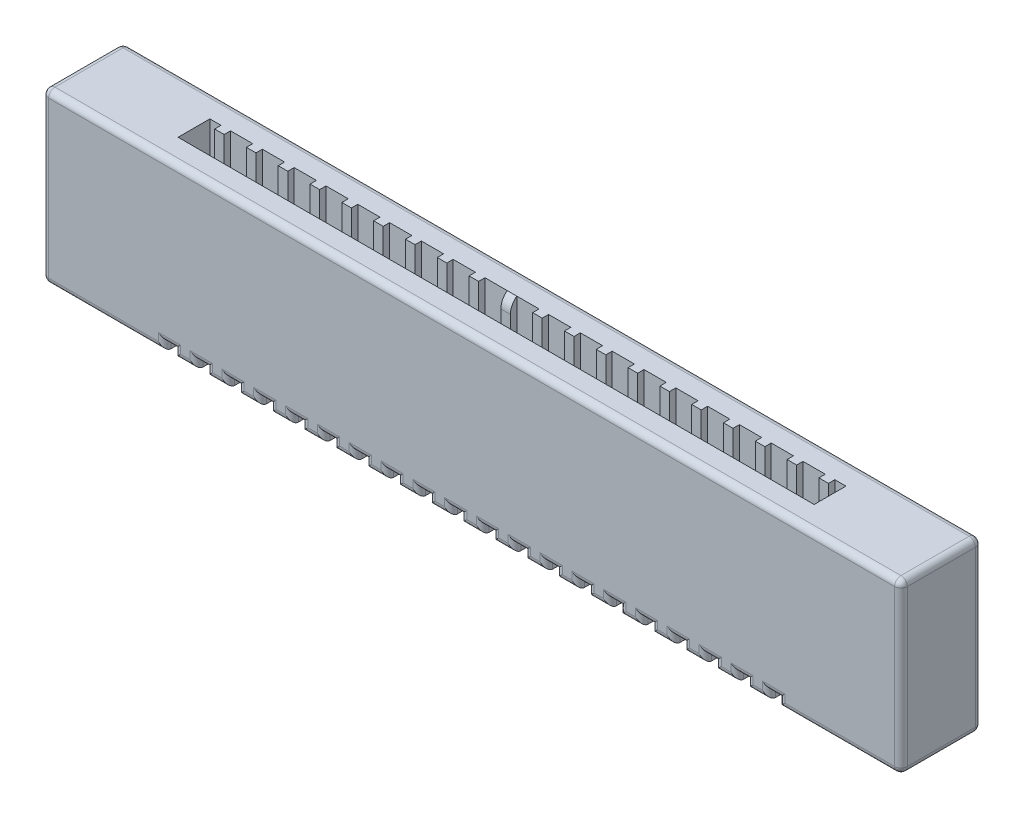
SolidWorks part; units mm, degrees
ref_plane "前视基准面" through (0, 0, 0) normal (0, 0, 1) x (1, 0, 0)
ref_plane "上视基准面" through (0, 0, 0) normal (0, 1, 0) x (1, 0, 0)
ref_plane "右视基准面" through (0, 0, 0) normal (1, 0, 0) x (0, 0, -1)
sketch "草图1" plane through (0, 0, 0) normal (0, 0, 1) x (1, 0, 0)
  line L0 (-1000, 0) -> (49000, 0) construction
  line L1 (0, -1000) -> (0, 49000) construction
  line L2 (-13.5, 2.65) -> (-13.5, -2.65)
  line L3 (-13.5, -2.65) -> (13.5, -2.65)
  line L4 (-13.5, 2.65) -> (13.5, 2.65)
  line L5 (13.5, 2.65) -> (13.5, -2.65)
  point P10 (-13.5, 0)
  point P11 (0, -2.65)
  point P12 (0, 2.65)
  dimension "D1" = 5.3
  dimension "D2" = 27
extrude "凸台-拉伸1" add sketch "草图1" along normal blind 2.54
sketch "草图2" plane through (0, -2.65, 0) normal (0, -1, 0) x (1, 0, 0)
  line L0 (0, 2.54) -> (0, 0) construction
  line L1 (-13.5, 2.54) -> (13.5, 2.54) construction
  line L2 (0.5, 2.54) -> (0.5, 0) construction
  line L3 (-13.5, 0) -> (13.5, 0) construction
  line L4 (0.65, 0.45) -> (0.65, 0.1)
  line L5 (0.65, 0.45) -> (0.35, 0.45)
  line L6 (0.35, 0.45) -> (0.35, 0.1)
  line L8 (0.35, 0.1) -> (0.65, 0.1)
  point P14 (0.5, 0.45)
  dimension "D1" = 0.5
  dimension "D2" = 0.3
  dimension "D3" = 0.1
  dimension "D4" = 0.35
ref_plane "基准面1" through (0.5, 0, 0) normal (1, 0, 0) x (0, 0, -1)
sketch "草图3" plane through (0.5, 0, 0) normal (1, 0, 0) x (0, 0, -1)
  line L0 (-0.45, -2.65) -> (-0.1861, -4.15)
sweep "扫描1" add profiles "草图2" path "草图3"
sketch "草图4" plane through (0.5, 0, 0) normal (1, 0, 0) x (0, 0, -1)
  line L0 (0, -3.2183) -> (0, -4.15)
  line L1 (0, -3.2183) -> (0.1639, -4.15)
  line L2 (0.1639, -4.15) -> (-0.1, -2.65) construction
  line L3 (0.1639, -4.15) -> (0, -4.15)
extrude "切除-拉伸1" cut sketch "草图4" along normal mid plane 0.3
pattern_linear "阵列(线性)1" count 10 spacing 1 along (1, 0, 0) of "切除-拉伸1", "扫描1"
mirror "镜向1" about plane through (0, 0, 0) normal (1, 0, 0) of "扫描1", "切除-拉伸1", "阵列(线性)1"
sketch "草图5" plane through (0, -2.65, 0) normal (0, -1, 0) x (1, 0, 0)
  line L0 (-13.5, 2.54) -> (13.5, 2.54) construction
  line L1 (-9.35, 0.45) -> (-9.6507, 0.45)
  line L2 (-9.35, 0.45) -> (-9.35, 2.54)
  line L3 (-9.35, 2.54) -> (-9.6507, 2.54)
  line L4 (-9.6507, 0.45) -> (-9.6507, 2.54)
extrude "切除-拉伸2" cut sketch "草图5" against normal blind 0.25
pattern_linear "阵列(线性)2" count 20 spacing 1 along (1, 0, 0) of "切除-拉伸2"
sketch "草图6" plane through (0, 2.65, 0) normal (0, 1, 0) x (-1, 0, 0)
  line L0 (0, 2.54) -> (0, 0) construction
  line L1 (-13.5, 2.54) -> (13.5, 2.54) construction
  line L2 (13.5, 1.27) -> (-13.5, 1.27) construction
  line L3 (13.5, 2.54) -> (13.5, 0) construction
  line L4 (-13.5, 2.54) -> (-13.5, 0) construction
  line L5 (10, 0.77) -> (10, 1.77)
  line L7 (10, 0.77) -> (-10, 0.77)
  line L8 (10, 1.77) -> (-10, 1.77)
  line L9 (-10, 0.77) -> (-10, 1.77)
  point P13 (10, 1.27)
  point P15 (0, 1.77)
  point P18 (0, 0.77)
  dimension "D1" = 20
  dimension "D2" = 1
extrude "切除-拉伸3" cut sketch "草图6" against normal blind 4
sketch "草图7" plane through (0, 2.65, 0) normal (0, 1, 0) x (1, 0, 0)
  line L0 (0, -2.54) -> (0, 0) construction
  line L1 (13.5, -2.54) -> (-13.5, -2.54) construction
  line L2 (13.5, 0) -> (-13.5, 0) construction
  line L3 (-0.5, -0.9797) -> (-0.5, -0.3005) construction
  line L4 (-0.3285, -0.77) -> (-0.6854, -0.77) construction
  line L5 (10, -0.77) -> (-10, -0.77) construction
  line L6 (-0.35, -0.97) -> (-0.35, -0.77)
  line L7 (-0.35, -0.97) -> (-0.65, -0.97)
  line L8 (-0.65, -0.97) -> (-0.65, -0.77)
  line L9 (-0.35, -0.77) -> (-0.65, -0.77)
  point P16 (-0.5, -0.97)
  dimension "D1" = 0.5
  dimension "D2" = 0.3
  dimension "D3" = 0.2
extrude "凸台-拉伸2" add sketch "草图7" against normal blind 3.5 separate body
fillet "圆角1" radius 0.5 1 edges at (-0.5, 2.65, 0.97)
pattern_linear "阵列(线性)5" count 10 spacing 1 along (-1, 0, 0) of "凸台-拉伸2"
pattern_linear "阵列(线性)6" count 11 spacing 1 along (1, 0, 0) of "凸台-拉伸2"
fillet "圆角5" radius 0.2 88 edges at (0, 2.65, 0) (-13.5, 0, 0) (0, -2.65, 0) (13.5, 0, 0) (9.4997, -2.4, 2.54) (9.3493, -2.525, 2.54) (8.9997, -2.65, 2.54) (8.65, -2.525, 2.54) (8.4997, -2.4, 2.54) (8.3493, -2.525, 2.54) (7.9997, -2.65, 2.54) (7.65, -2.525, 2.54) (7.4997, -2.4, 2.54) (7.3493, -2.525, 2.54) (6.9997, -2.65, 2.54) (6.65, -2.525, 2.54) (6.4997, -2.4, 2.54) (6.3493, -2.525, 2.54) (5.9997, -2.65, 2.54) (5.65, -2.525, 2.54) (5.4997, -2.4, 2.54) (5.3493, -2.525, 2.54) (4.9997, -2.65, 2.54) (4.65, -2.525, 2.54) (4.4997, -2.4, 2.54) (4.3493, -2.525, 2.54) (3.9997, -2.65, 2.54) (3.65, -2.525, 2.54) (3.4997, -2.4, 2.54) (3.3493, -2.525, 2.54) (2.9997, -2.65, 2.54) (2.65, -2.525, 2.54) (2.4997, -2.4, 2.54) (2.3493, -2.525, 2.54) (1.9997, -2.65, 2.54) (1.65, -2.525, 2.54) (1.4997, -2.4, 2.54) (1.3493, -2.525, 2.54) (0.9997, -2.65, 2.54) (0.65, -2.525, 2.54) (0.4997, -2.4, 2.54) (0.3493, -2.525, 2.54) (-0.0003, -2.65, 2.54) (-0.35, -2.525, 2.54) (-0.5003, -2.4, 2.54) (-0.6507, -2.525, 2.54) (-1.0003, -2.65, 2.54) (-1.35, -2.525, 2.54) (-1.5003, -2.4, 2.54) (-1.6507, -2.525, 2.54) (-2.0003, -2.65, 2.54) (-2.35, -2.525, 2.54) (-2.5003, -2.4, 2.54) (-2.6507, -2.525, 2.54) (-3.0003, -2.65, 2.54) (-3.35, -2.525, 2.54) (-3.5003, -2.4, 2.54) (-3.6507, -2.525, 2.54) (-4.0003, -2.65, 2.54) (-4.35, -2.525, 2.54) (-4.5003, -2.4, 2.54) (-4.6507, -2.525, 2.54) (-5.0003, -2.65, 2.54) (-5.35, -2.525, 2.54) (-5.5003, -2.4, 2.54) (-5.6507, -2.525, 2.54) (-6.0003, -2.65, 2.54) (-6.35, -2.525, 2.54) (-6.5003, -2.4, 2.54) (-6.6507, -2.525, 2.54) (-7.0003, -2.65, 2.54) (-7.35, -2.525, 2.54) (-7.5003, -2.4, 2.54) (-7.6507, -2.525, 2.54) (-8.0003, -2.65, 2.54) (-8.35, -2.525, 2.54) (-8.5003, -2.4, 2.54) (-8.6507, -2.525, 2.54) (-9.0003, -2.65, 2.54) (-9.35, -2.525, 2.54) (-9.5003, -2.4, 2.54) (-9.6507, -2.525, 2.54) (-11.5753, -2.65, 2.54) (-13.5, 0, 2.54) (0, 2.65, 2.54) (13.5, 0, 2.54) (11.575, -2.65, 2.54) (9.65, -2.525, 2.54)
fillet "圆角6" radius 0.2 12 edges at (-13.4414, -2.5914, 2.4814) (-13.4414, -2.5914, 0.0586) (-13.4414, 2.5914, 2.4814) (-13.4414, 2.5914, 0.0586) (13.4414, 2.5914, 2.4814) (13.4414, 2.5914, 0.0586) (13.4414, -2.5914, 2.4814) (13.4414, -2.5914, 0.0586) (-13.5, -2.65, 1.27) (-13.5, 2.65, 1.27) (13.5, 2.65, 1.27) (13.5, -2.65, 1.27)
